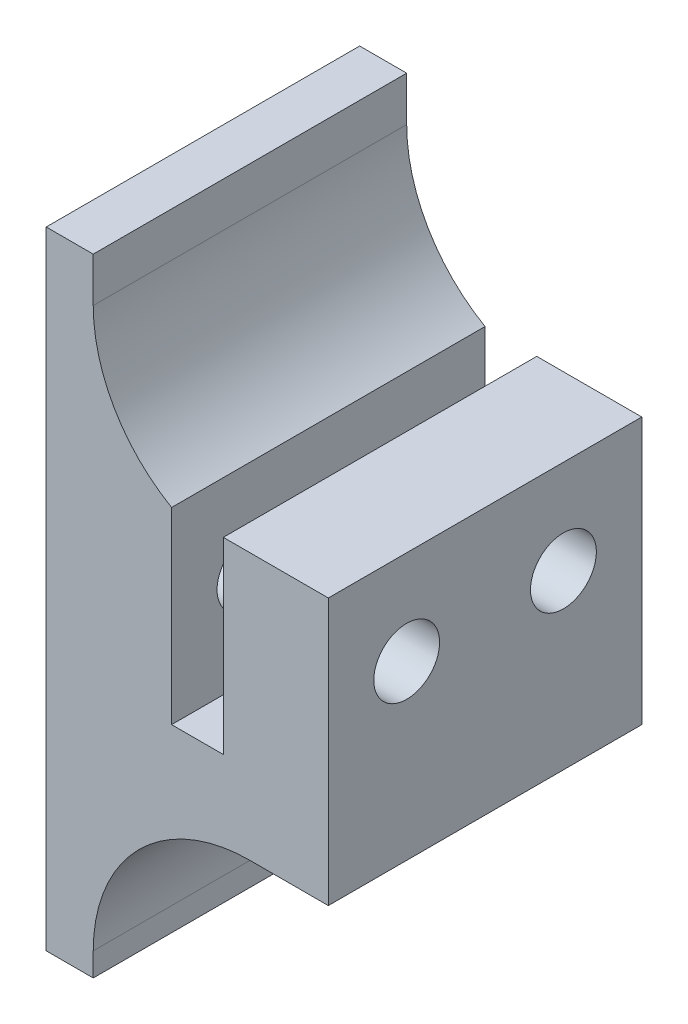
SolidWorks part; units mm, degrees
material "ABS"
ref_plane "前视基准面" through (0, 0, 0) normal (0, 0, 1) x (1, 0, 0)
ref_plane "上视基准面" through (0, 0, 0) normal (0, 1, 0) x (1, 0, 0)
ref_plane "右视基准面" through (0, 0, 0) normal (1, 0, 0) x (0, 0, -1)
other "Configuration Table"
sketch "草图1" plane through (0, 0, 0) normal (0, 0, 1) x (1, 0, 0)
  line L0 (3.3, 0) -> (10, 0)
  line L1 (0, 0) -> (3.3, 0) construction
  line L2 (0, 0) -> (0, -12) construction
  line L3 (0, -12) -> (3.3, -12) construction
  line L4 (3.3, 0) -> (3.3, -12) construction
  line L5 (10, 0) -> (10, -17)
  line L6 (10, -17) -> (0, -17)
  line L7 (0, -17) -> (-5, -17)
  line L8 (-5, -17) -> (-5, -28.5)
  line L9 (-5, -28.5) -> (-8, -28.5)
  line L10 (-8, -28.5) -> (-8, 11.5)
  line L11 (-8, 11.5) -> (-5, 11.5)
  line L12 (-5, 11.5) -> (-5, 0)
  line L13 (-5, 0) -> (0, 0)
  line L14 (0, 0) -> (0, -12)
  line L15 (0, -12) -> (3.3, -12)
  line L16 (3.3, -12) -> (3.3, 0)
  dimension "D1" = 3.3
  dimension "D2" = 12
  dimension "D3" = 10
  dimension "D4" = 5
  dimension "D5" = 5
  dimension "D6" = 40
  dimension "D7" = 3
extrude "凸台-拉伸1" add sketch "草图1" along normal blind 20
fillet "圆角1" radius 10 2 edges at (-5, -17, 10) (-5, 0, 10)
sketch "草图2" plane through (-8, 0, 0) normal (-1, 0, 0) x (0, 0, 1)
  line L0 (20, 11.5) -> (20, -28.5) construction
  line L1 (0, -6) -> (20, -6) construction
  line L2 (0, 11.5) -> (0, -28.5) construction
  line L3 (20, -28.5) -> (0, -28.5) construction
  circle A0 centre (5, -6) radius 2.1
  circle A1 centre (15, -6) radius 2.1
  point P12 (15, -6)
  dimension "D2" = 4.2
  dimension "D3" = 10
  dimension "D4" = 5
  dimension "D1" = 22.5
extrude "切除-拉伸1" cut sketch "草图2" against normal through all
